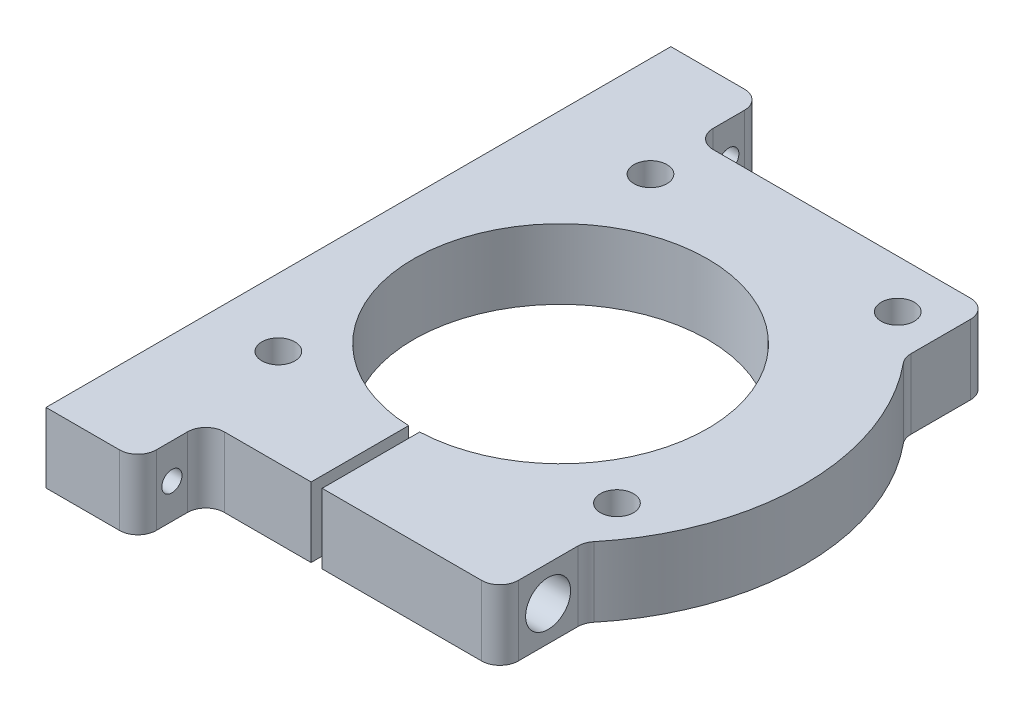
SolidWorks part; units mm, degrees
ref_plane "Piano frontale" through (0, 0, 0) normal (0, 0, 1) x (1, 0, 0)
ref_plane "Piano superiore" through (0, 0, 0) normal (0, 1, 0) x (1, 0, 0)
ref_plane "Piano destro" through (0, 0, 0) normal (1, 0, 0) x (0, 0, -1)
sketch "Sketch1" plane through (0, 0, -219.72) normal (0, -1, 0) x (1, 0, 0)
  line L2 (7.3254, -97.2179) -> (7.3254, -57.6696) construction
  line L3 (-32.6746, -97.2179) -> (7.3254, -97.2179) construction
  line L4 (17.3254, -30.7179) -> (-31.0496, -30.7179)
  line L5 (-62.6746, -30.7179) -> (-62.6746, -12.2179)
  line L6 (-62.6746, -12.2179) -> (-87.6746, -12.2179)
  line L7 (-34.0496, -30.7179) -> (-62.6746, -30.7179)
  line L8 (-41.0496, -30.7179) -> (-41.0496, -68.4106) construction
  line L9 (-24.0496, -68.4844) -> (-24.0496, -30.7179) construction
  line L10 (-87.6746, -182.2179) -> (-62.6746, -182.2179)
  line L11 (-62.6746, -182.2179) -> (-62.6746, -163.7179)
  line L12 (-87.6746, -22.2179) -> (-87.6746, -172.2179) construction
  line L13 (-62.6746, -163.7179) -> (17.3254, -163.7179)
  line L14 (17.3254, -163.7179) -> (17.3254, -140.6812)
  line L15 (17.3254, -53.7545) -> (17.3254, -30.7179)
  line L16 (-72.6746, -153.7179) -> (7.3254, -153.7179) construction
  line L17 (-34.0496, -40.7179) -> (-72.6746, -40.7179) construction
  line L18 (-34.0496, -57.2415) -> (-34.0496, -40.7179) construction
  line L19 (-31.0496, -40.7179) -> (-31.0496, -57.2509) construction
  line L21 (17.3254, -30.7179) -> (-41.0496, -30.7179) construction
  line L23 (-24.0496, -30.7179) -> (-62.6746, -30.7179) construction
  line L24 (-31.0496, -30.7179) -> (-31.0496, -57.2509)
  line L25 (-34.0496, -57.2415) -> (-34.0496, -30.7179)
  line L29 (-87.6746, -12.2179) -> (-87.6746, -182.2179)
  line L36 (-62.6746, -12.2179) -> (-97.6746, -12.2179) construction
  line L37 (-97.6746, -12.2179) -> (-97.6746, -182.2179) construction
  line L38 (-97.6746, -182.2179) -> (-62.6746, -182.2179) construction
  line L39 (-62.6746, -182.2179) -> (-62.6746, -163.7179) construction
  line L40 (-62.6746, -30.7179) -> (-62.6746, -12.2179) construction
  line L41 (-72.6746, -172.2179) -> (-72.6746, -153.7179) construction
  line L42 (-87.6746, -172.2179) -> (-72.6746, -172.2179) construction
  line L43 (-72.6746, -22.2179) -> (-87.6746, -22.2179) construction
  line L44 (-72.6746, -40.7179) -> (-72.6746, -22.2179) construction
  line L45 (7.3254, -40.7179) -> (-31.0496, -40.7179) construction
  line L46 (7.3254, -57.6696) -> (7.3254, -40.7179) construction
  line L47 (7.3254, -153.7179) -> (7.3254, -136.7661) construction
  arc A2 (7.3254, -136.7661) -> (7.3254, -57.6696) centre (-32.6746, -97.2179) ccw construction
  arc A3 (17.3254, -140.6812) -> (17.3254, -53.7545) centre (-32.6746, -97.2179) ccw
  arc A4 (-34.0496, -57.2415) -> (-31.0496, -57.2509) centre (-32.6746, -97.2179) ccw
  arc A5 (-24.0496, -68.4844) -> (-41.0496, -68.4106) centre (-32.6746, -97.2179) ccw construction
  dimension "D1" = 10
extrude "Boss-Extrude2" add sketch "Sketch1" along normal blind 19 contours L25 A4 L24 L29 region at (15.2373, 0, -261.9562)
fillet "Fillet2" radius 5 8 edges at (-62.6746, -9.5, -231.9379) (-62.6746, -9.5, -250.4379) (17.3254, -9.5, -250.4379) (-62.6746, -9.5, -401.9379) (-62.6746, -9.5, -383.4379) (17.3254, -9.5, -383.4379) (17.3254, -9.5, -360.4012) (17.3254, -9.5, -273.4745)
hole_wizard "M5 Clearance Hole1" positions "Sketch4" profile "Sketch5" hole size "M5" standard "ISO" end condition through all
sketch "Sketch4" plane through (17.3254, 0, 0) normal (1, 0, 0) x (0, 0, -1)
  point P2 (241.1879, -9.5)
  point P4 (392.6879, -9.5)
  point P7 (0, 0)
sketch "Sketch5" plane through (17.3254, -9.5, -241.1879) normal (0, 1, 0) x (0, 0, -1)
  line L0 (0, 0) -> (0, 105)
  line L1 (0, 105) -> (2.75, 105)
  line L2 (2.75, 105) -> (2.75, 0)
  line L5 (2.75, 0) -> (0, 0)
  line L11 (0, -6.35) -> (0, 107.95) construction
  dimension "Thru Hole Dia." = 5.5
  dimension "Thru Hole Depth" = 105
hole_wizard "CBORE for M5 Hex Head Bolt1" positions "Sketch6" profile "Sketch7" counterbore size "M5" standard "ISO" end condition up to next
sketch "Sketch6" plane through (17.3254, 0, 0) normal (1, 0, 0) x (0, 0, -1)
  point P0 (263.5408, -9.5)
sketch "Sketch7" plane through (17.3254, -9.5, -263.5408) normal (0, 1, 0) x (0, 0, -1)
  line L0 (0, 0) -> (0, 48.375)
  line L1 (0, 48.375) -> (2.75, 48.375)
  line L3 (2.75, 48.375) -> (2.75, 23.5)
  line L4 (2.75, 23.5) -> (6.119, 23.5)
  line L5 (6.119, 23.5) -> (6.119, 0)
  line L7 (6.119, 0) -> (0, 0)
  line L11 (0, -6.35) -> (0, 107.95) construction
  dimension "Thru Hole Dia." = 5.5
  dimension "Thru Hole Depth" = 48.375
  dimension "C'Bore Dia." = 12.238
  dimension "C'Bore Depth" = 23.5
hole_wizard "Tap Drill for M5 Tap1" positions "Sketch8" profile "Sketch9" hole size "M5" standard "ISO" end condition up to next
sketch "Sketch8" plane through (-34.0496, 0, 0) normal (1, 0, 0) x (0, 0, -1)
  point P0 (263.5408, -9.5)
sketch "Sketch9" plane through (-34.0496, -9.5, -263.5408) normal (0, 1, 0) x (0, 0, -1)
  line L0 (0, 0) -> (0, 53.625)
  line L1 (0, 53.625) -> (2.1, 53.625)
  line L2 (2.1, 53.625) -> (2.1, 0)
  line L5 (2.1, 0) -> (0, 0)
  line L11 (0, -6.35) -> (0, 107.95) construction
  dimension "Thru Hole Dia." = 4.2
  dimension "Thru Hole Depth" = 53.625
hole_wizard "M8 Clearance Hole1" positions "Sketch10" profile "Sketch11" hole size "M8" standard "ISO" end condition up to next
sketch "Sketch10" plane through (0, 0, 0) normal (0, 1, 0) x (1, 0, 0)
  point P0 (5.6543, 370.335)
  point P2 (12.5599, 287.0353)
  point P4 (-60.405, 369.1208)
  point P6 (-69.265, 276.742)
sketch "Sketch11" plane through (5.6543, 0, -370.335) normal (1, 0, 0) x (0, 0, 1)
  line L0 (0, 0) -> (0, 19)
  line L1 (0, 19) -> (4.5, 19)
  line L2 (4.5, 19) -> (4.5, 0)
  line L5 (4.5, 0) -> (0, 0)
  line L11 (0, -6.35) -> (0, 107.95) construction
  dimension "Thru Hole Dia." = 9
  dimension "Thru Hole Depth" = 19
